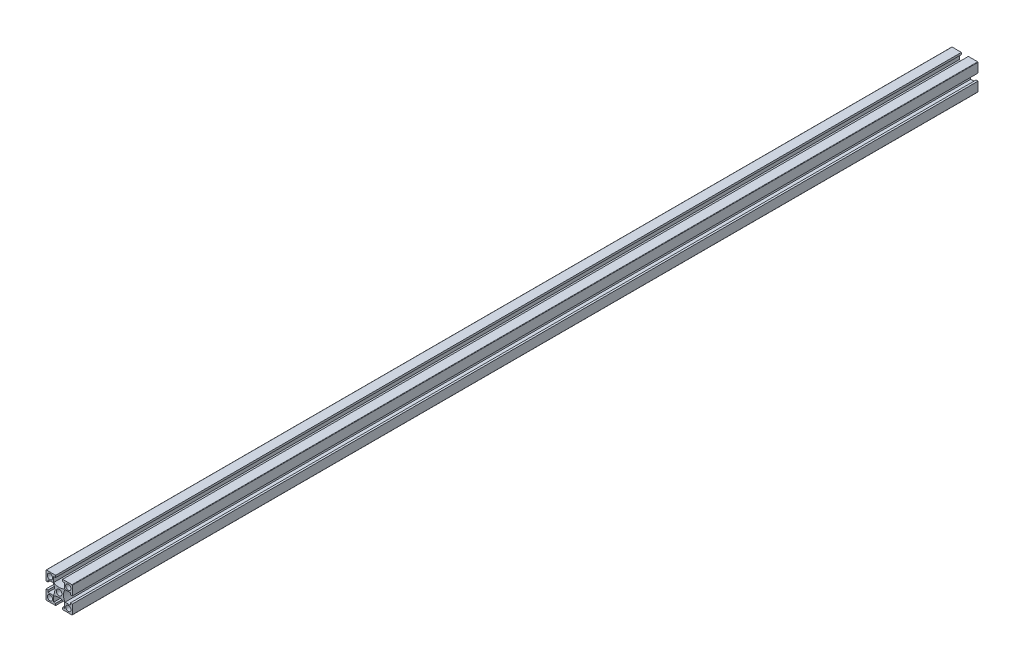
SolidWorks part; units mm, degrees
ref_plane "정면" through (0, 0, 0) normal (0, 0, 1) x (1, 0, 0)
ref_plane "윗면" through (0, 0, 0) normal (0, 1, 0) x (1, 0, 0)
ref_plane "우측면" through (0, 0, 0) normal (1, 0, 0) x (0, 0, -1)
sketch "스케치1" plane through (0, 0, 0) normal (0, 0, 1) x (1, 0, 0)
  line L0 (0, 32.0265) -> (0, -31.6588) construction
  line L1 (-10, 10) -> (-10, -10)
  line L2 (-10, 10) -> (10, 10)
  line L3 (-10, 2.65) -> (-8.5, 2.65)
  line L4 (13.6618, 0) -> (-11.6993, 0) construction
  line L5 (-8.5, 2.65) -> (-8.5, 4.15)
  line L6 (-8.5, 4.15) -> (-4.5032, 4.15)
  line L7 (-10, -2.65) -> (-8.5, -2.65)
  line L8 (-8.5, -2.65) -> (-8.5, -4.15)
  line L9 (-8.5, -4.15) -> (-4.5032, -4.15)
  line L10 (-10, -10) -> (10, -10)
  line L11 (10, 10) -> (10, -10)
  circle A0 centre (-7, 7) radius 2
  circle A1 centre (-7, -7) radius 2
  arc A2 (-4.5032, 4.15) -> (-4.5032, -4.15) centre (-11.0587, 0) cw
  circle A3 centre (0, 0) radius 2.15
  circle A4 centre (7, 7) radius 2
  circle A5 centre (7, -7) radius 2
  point P21 (-10, 0)
  point P23 (-3.3, 0)
  point P31 (0, -10)
  point P32 (0, 10)
  dimension "D3" = 4
  dimension "D9" = 6.7
  dimension "D10" = 4.3
  dimension "D11" = 7.7587
  dimension "D1" = 20
  dimension "D2" = 20
  dimension "D4" = 14
  dimension "D5" = 14
  dimension "D6" = 5.3
  dimension "D7" = 8.3
  dimension "D8" = 1.5
extrude "보스-돌출1" add sketch "스케치1" along normal blind 690 contours A0 | A4 | A3 | A5 | A1 | A2 L6 L5 L3 L1 L7 L8 L9 | L2 L11 L10 L1 region at (-6.6069, 0, 0) region at (-7, 7, 0) region at (-7, -7, 0) region at (0, 0, 0) region at (7, 7, 0) region at (7, -7, 0)
extrude "컷-돌출1" cut sketch "스케치1<3>" along normal up to next contours A2 L6 L5 L3 L1 L7 L8 L9 region at (-6.6069, 0, 0)
sketch "스케치1<3>" plane through (0, 0, 0) normal (0, 0, 1) x (1, 0, 0) same geometry as "스케치1"
pattern_circular "원형 패턴1" count 4 over 360 about axis through (0, 0, 690) along (0, 0, -1) of "컷-돌출1" reverse direction yes
fillet "필렛1" radius 0.3 4 edges at (10, -10, 345) (-10, -10, 345) (-10, 10, 345) (10, 10, 345)
